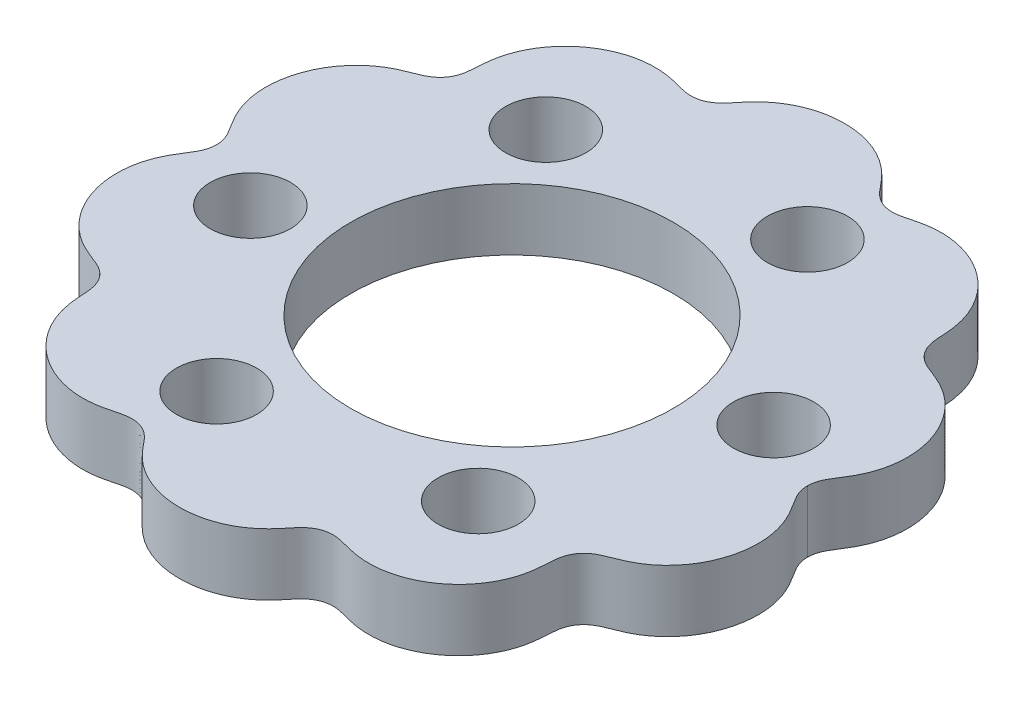
SolidWorks part; units mm, degrees
ref_plane "Front Plane" through (0, 0, 0) normal (0, 0, 1) x (1, 0, 0)
ref_plane "Top Plane" through (0, 0, 0) normal (0, 1, 0) x (1, 0, 0)
ref_plane "Right Plane" through (0, 0, 0) normal (1, 0, 0) x (0, 0, -1)
sketch "Sketch1" plane through (0, 0, 0) normal (0, 1, 0) x (1, 0, 0)
  spline S0 degree 4 poles (25.7906, 7.5343) (25.8788, 7.1133) (25.9899, 6.258) (25.9622, 5.173) (25.6669, 3.909) (25.2966, 3.0278) (25.0022, 2.4855) (24.7411, 2.0653) (24.5631, 1.7918) (24.4128, 1.5559) (24.2753, 1.3229) (24.1728, 1.1289) (24.0852, 0.9325) (24.0168, 0.7401) (23.9736, 0.5903) (23.9409, 0.4443) (23.918, 0.3017) (23.9061, 0.188) (23.9012, 0.082) (23.8998, 0.0096) (23.9001, -0.0378) (23.9031, -0.1354) (23.9124, -0.2583) (23.931, -0.3897) (23.9595, -0.5322) (23.992, -0.6548) (24.033, -0.7865) (24.0838, -0.9249) (24.1521, -1.083) (24.2429, -1.2629) (24.3447, -1.4425) (24.4552, -1.6225) (24.5717, -1.8045) (24.7183, -2.0313) (24.8914, -2.3053) (25.0875, -2.6402) (25.2934, -3.0428) (25.5234, -3.5754) (25.7435, -4.2491) (25.909, -5.0602) (25.989, -6.24) (25.8643, -7.4222) (25.5418, -8.5683) (25.0323, -9.6423) (24.5159, -10.4451) (23.8988, -11.1736) (23.1893, -11.8124) (22.5069, -12.2735) (21.8941, -12.5927) (21.3804, -12.8129) (20.9812, -12.967) (20.5083, -13.1497) (20.0028, -13.3924) (19.5163, -13.7704) (19.1071, -14.3429) (18.9044, -14.9387) (18.8377, -15.5108) (18.8117, -16.0408) (18.7845, -16.4899) (18.7247, -17.0578) (18.5966, -17.7393) (18.287, -18.7429) (17.6345, -19.995) (16.5677, -21.2689) (15.0187, -22.3804) (13.232, -23.0712) (11.6863, -23.2335) (10.5209, -23.1072) (9.745, -22.9271) (9.3314, -22.8175) (8.8415, -22.6876) (8.2891, -22.5904) (7.675, -22.6156) (7.014, -22.8425) (6.5078, -23.2036) (6.1238, -23.6204) (5.7973, -24.0261) (5.517, -24.3664) (4.9887, -24.958) (4.1217, -25.7163) (2.8002, -26.4589) (0.9866, -26.9323) (-0.8925, -26.9446) (-2.4927, -26.549) (-3.7586, -25.9235) (-4.6012, -25.2962) (-5.1069, -24.8217) (-5.4903, -24.3984) (-5.7768, -24.0514) (-6.1092, -23.6377) (-6.4971, -23.212) (-7.008, -22.8447) (-7.6734, -22.6157) (-8.2891, -22.5904) (-8.8414, -22.6876) (-9.3314, -22.8175) (-9.745, -22.9271) (-10.5209, -23.1072) (-11.6863, -23.2335) (-13.232, -23.0712) (-15.0187, -22.3804) (-16.5677, -21.2689) (-17.6345, -19.995) (-18.287, -18.7429) (-18.5966, -17.7393) (-18.7247, -17.0578) (-18.7845, -16.4899) (-18.8117, -16.0408) (-18.8377, -15.5108) (-18.9044, -14.9387) (-19.1071, -14.3429) (-19.5163, -13.7704) (-20.0028, -13.3924) (-20.5083, -13.1497) (-20.9812, -12.967) (-21.3804, -12.8129) (-21.8941, -12.5927) (-22.5069, -12.2735) (-23.1893, -11.8124) (-23.8988, -11.1736) (-24.5159, -10.4451) (-25.0323, -9.6423) (-25.5418, -8.5683) (-25.8643, -7.4222) (-25.989, -6.24) (-25.909, -5.0602) (-25.7435, -4.2491) (-25.5234, -3.5754) (-25.2934, -3.0428) (-25.0875, -2.6402) (-24.8914, -2.3053) (-24.7183, -2.0313) (-24.5717, -1.8045) (-24.4552, -1.6225) (-24.3447, -1.4425) (-24.2429, -1.2629) (-24.1521, -1.083) (-24.0838, -0.9249) (-24.033, -0.7865) (-23.992, -0.6548) (-23.9595, -0.5322) (-23.931, -0.3897) (-23.9124, -0.2583) (-23.9031, -0.1354) (-23.9001, -0.0378) (-23.8998, 0.0096) (-23.9012, 0.082) (-23.9061, 0.188) (-23.918, 0.3017) (-23.9409, 0.4443) (-23.9736, 0.5903) (-24.0168, 0.7401) (-24.0852, 0.9325) (-24.1918, 1.1715) (-24.3429, 1.4455) (-24.5376, 1.7528) (-24.7411, 2.0653) (-25.0022, 2.4855) (-25.2966, 3.0278) (-25.6669, 3.909) (-25.9622, 5.173) (-25.9899, 6.258) (-25.8788, 7.1133) (-25.7906, 7.5343) knots 0 0 0 0 0 0.016557 0.033114 0.041392 0.04967 0.053259 0.056848 0.060437 0.062231 0.064026 0.067263 0.068881 0.0705 0.071881 0.073262 0.074643 0.076024 0.076447 0.07687 0.077627 0.078384 0.079897 0.081411 0.082924 0.083871 0.084817 0.08671 0.088602 0.090495 0.092574 0.094654 0.096734 0.098813 0.102972 0.107132 0.111671 0.11621 0.125289 0.134368 0.143447 0.161605 0.170766 0.179928 0.18909 0.198252 0.207413 0.216574 0.220692 0.22481 0.228927 0.233045 0.240218 0.246328 0.252328 0.259785 0.264113 0.268441 0.27277 0.277098 0.286094 0.29509 0.313082 0.331073 0.349394 0.367716 0.386036 0.390153 0.39427 0.398387 0.402504 0.409677 0.415786 0.421726 0.429063 0.433304 0.437545 0.441787 0.446028 0.463838 0.481648 0.499458 0.517452 0.535446 0.544443 0.55344 0.557769 0.562098 0.566426 0.570755 0.578213 0.584214 0.590323 0.597496 0.601613 0.60573 0.609847 0.613964 0.632284 0.650606 0.668927 0.686918 0.70491 0.713906 0.722902 0.72723 0.731559 0.735887 0.740215 0.747672 0.753672 0.759782 0.766955 0.771073 0.77519 0.779308 0.783426 0.792587 0.801748 0.81091 0.820072 0.829234 0.838395 0.856553 0.865632 0.874711 0.88379 0.888329 0.892868 0.897028 0.901187 0.903266 0.905346 0.907426 0.909505 0.911398 0.91329 0.915183 0.916129 0.917076 0.918589 0.920103 0.921616 0.922373 0.92313 0.923553 0.923976 0.925357 0.926738 0.928119 0.9295 0.931119 0.932737 0.935974 0.939563 0.943152 0.946741 0.95033 0.958608 0.966886 0.983443 1 1 1 1 1 construction
  spline S1 degree 4 poles (23.9, 0) (23.9, -0.0166) (23.9004, -0.0497) (23.9031, -0.1354) (23.9124, -0.2583) (23.931, -0.3897) (23.9595, -0.5322) (23.992, -0.6548) (24.033, -0.7865) (24.0838, -0.9249) (24.1521, -1.083) (24.2429, -1.2629) (24.3447, -1.4425) (24.4552, -1.6225) (24.5717, -1.8045) (24.7183, -2.0313) (24.8914, -2.3053) (25.0875, -2.6402) (25.2934, -3.0428) (25.5234, -3.5754) (25.7435, -4.2491) (25.909, -5.0602) (25.989, -6.24) (25.8643, -7.4222) (25.5418, -8.5683) (25.0323, -9.6423) (24.5159, -10.4451) (23.8988, -11.1736) (23.1893, -11.8124) (22.5069, -12.2735) (21.8941, -12.5927) (21.3804, -12.8129) (20.9812, -12.967) (20.5083, -13.1497) (20.0028, -13.3924) (19.5163, -13.7704) (19.1071, -14.3429) (18.9044, -14.9387) (18.8377, -15.5108) (18.8117, -16.0408) (18.7845, -16.4899) (18.7247, -17.0578) (18.5966, -17.7393) (18.287, -18.7429) (17.6345, -19.995) (16.5677, -21.2689) (15.0187, -22.3804) (13.232, -23.0712) (11.6863, -23.2335) (10.5209, -23.1072) (9.745, -22.9271) (9.3314, -22.8175) (8.8415, -22.6876) (8.2891, -22.5904) (7.675, -22.6156) (7.014, -22.8425) (6.5078, -23.2036) (6.1238, -23.6204) (5.7973, -24.0261) (5.517, -24.3664) (4.9887, -24.958) (4.1217, -25.7163) (2.8002, -26.4589) (0.9866, -26.9323) (-0.8925, -26.9446) (-2.4927, -26.549) (-3.7586, -25.9235) (-4.6012, -25.2962) (-5.1069, -24.8217) (-5.4903, -24.3984) (-5.7768, -24.0514) (-6.1092, -23.6377) (-6.4971, -23.212) (-7.008, -22.8447) (-7.6734, -22.6157) (-8.2891, -22.5904) (-8.8414, -22.6876) (-9.3314, -22.8175) (-9.745, -22.9271) (-10.5209, -23.1072) (-11.6863, -23.2335) (-13.232, -23.0712) (-15.0187, -22.3804) (-16.5677, -21.2689) (-17.6345, -19.995) (-18.287, -18.7429) (-18.5966, -17.7393) (-18.7247, -17.0578) (-18.7845, -16.4899) (-18.8117, -16.0408) (-18.8377, -15.5108) (-18.9044, -14.9387) (-19.1071, -14.3429) (-19.5163, -13.7704) (-20.0028, -13.3924) (-20.5083, -13.1497) (-20.9812, -12.967) (-21.3804, -12.8129) (-21.8941, -12.5927) (-22.5069, -12.2735) (-23.1893, -11.8124) (-23.8988, -11.1736) (-24.5159, -10.4451) (-25.0323, -9.6423) (-25.5418, -8.5683) (-25.8643, -7.4222) (-25.989, -6.24) (-25.909, -5.0602) (-25.7435, -4.2491) (-25.5234, -3.5754) (-25.2934, -3.0428) (-25.0875, -2.6402) (-24.8914, -2.3053) (-24.7183, -2.0313) (-24.5717, -1.8045) (-24.4552, -1.6225) (-24.3447, -1.4425) (-24.2429, -1.2629) (-24.1521, -1.083) (-24.0838, -0.9249) (-24.033, -0.7865) (-23.992, -0.6548) (-23.9595, -0.5322) (-23.931, -0.3897) (-23.9124, -0.2583) (-23.9031, -0.1354) (-23.9004, -0.0497) (-23.9, -0.0166) (-23.9, 0) knots 0.07687 0.07687 0.07687 0.07687 0.07687 0.077627 0.078384 0.079897 0.081411 0.082924 0.083871 0.084817 0.08671 0.088602 0.090495 0.092574 0.094654 0.096734 0.098813 0.102972 0.107132 0.111671 0.11621 0.125289 0.134368 0.143447 0.161605 0.170766 0.179928 0.18909 0.198252 0.207413 0.216574 0.220692 0.22481 0.228927 0.233045 0.240218 0.246328 0.252328 0.259785 0.264113 0.268441 0.27277 0.277098 0.286094 0.29509 0.313082 0.331073 0.349394 0.367716 0.386036 0.390153 0.39427 0.398387 0.402504 0.409677 0.415786 0.421726 0.429063 0.433304 0.437545 0.441787 0.446028 0.463838 0.481648 0.499458 0.517452 0.535446 0.544443 0.55344 0.557769 0.562098 0.566426 0.570755 0.578213 0.584214 0.590323 0.597496 0.601613 0.60573 0.609847 0.613964 0.632284 0.650606 0.668927 0.686918 0.70491 0.713906 0.722902 0.72723 0.731559 0.735887 0.740215 0.747672 0.753672 0.759782 0.766955 0.771073 0.77519 0.779308 0.783426 0.792587 0.801748 0.81091 0.820072 0.829234 0.838395 0.856553 0.865632 0.874711 0.88379 0.888329 0.892868 0.897028 0.901187 0.903266 0.905346 0.907426 0.909505 0.911398 0.91329 0.915183 0.916129 0.917076 0.918589 0.920103 0.921616 0.922373 0.92313 0.92313 0.92313 0.92313 0.92313
  spline S2 degree 4 poles (-25.7906, -7.5343) (-25.8788, -7.1133) (-25.9899, -6.258) (-25.9622, -5.173) (-25.6669, -3.909) (-25.2966, -3.0278) (-25.0022, -2.4855) (-24.7411, -2.0653) (-24.5631, -1.7918) (-24.4128, -1.5559) (-24.2753, -1.3229) (-24.1728, -1.1289) (-24.0852, -0.9325) (-24.0168, -0.7401) (-23.9736, -0.5903) (-23.9409, -0.4443) (-23.918, -0.3017) (-23.9061, -0.188) (-23.9012, -0.082) (-23.8998, -0.0096) (-23.9001, 0.0378) (-23.9031, 0.1354) (-23.9124, 0.2583) (-23.931, 0.3897) (-23.9595, 0.5322) (-23.992, 0.6548) (-24.033, 0.7865) (-24.0838, 0.9249) (-24.1521, 1.083) (-24.2429, 1.2629) (-24.3447, 1.4425) (-24.4552, 1.6225) (-24.5717, 1.8045) (-24.7183, 2.0313) (-24.8914, 2.3053) (-25.0875, 2.6402) (-25.2934, 3.0428) (-25.5234, 3.5754) (-25.7435, 4.2491) (-25.909, 5.0602) (-25.989, 6.24) (-25.8643, 7.4222) (-25.5418, 8.5683) (-25.0323, 9.6423) (-24.5159, 10.4451) (-23.8988, 11.1736) (-23.1893, 11.8124) (-22.5069, 12.2735) (-21.8941, 12.5927) (-21.3804, 12.8129) (-20.9812, 12.967) (-20.5083, 13.1497) (-20.0028, 13.3924) (-19.5163, 13.7704) (-19.1071, 14.3429) (-18.9044, 14.9387) (-18.8377, 15.5108) (-18.8117, 16.0408) (-18.7845, 16.4899) (-18.7247, 17.0578) (-18.5966, 17.7393) (-18.287, 18.7429) (-17.6345, 19.995) (-16.5677, 21.2689) (-15.0187, 22.3804) (-13.232, 23.0712) (-11.6863, 23.2335) (-10.5209, 23.1072) (-9.745, 22.9271) (-9.3314, 22.8175) (-8.8415, 22.6876) (-8.2891, 22.5904) (-7.675, 22.6156) (-7.014, 22.8425) (-6.5078, 23.2036) (-6.1238, 23.6204) (-5.7973, 24.0261) (-5.517, 24.3664) (-4.9887, 24.958) (-4.1217, 25.7163) (-2.8002, 26.4589) (-0.9866, 26.9323) (0.8925, 26.9446) (2.4927, 26.549) (3.7586, 25.9235) (4.6012, 25.2962) (5.1069, 24.8217) (5.4903, 24.3984) (5.7768, 24.0514) (6.1092, 23.6377) (6.4971, 23.212) (7.008, 22.8447) (7.6734, 22.6157) (8.2891, 22.5904) (8.8414, 22.6876) (9.3314, 22.8175) (9.745, 22.9271) (10.5209, 23.1072) (11.6863, 23.2335) (13.232, 23.0712) (15.0187, 22.3804) (16.5677, 21.2689) (17.6345, 19.995) (18.287, 18.7429) (18.5966, 17.7393) (18.7247, 17.0578) (18.7845, 16.4899) (18.8117, 16.0408) (18.8377, 15.5108) (18.9044, 14.9387) (19.1071, 14.3429) (19.5163, 13.7704) (20.0028, 13.3924) (20.5083, 13.1497) (20.9812, 12.967) (21.3804, 12.8129) (21.8941, 12.5927) (22.5069, 12.2735) (23.1893, 11.8124) (23.8988, 11.1736) (24.5159, 10.4451) (25.0323, 9.6423) (25.5418, 8.5683) (25.8643, 7.4222) (25.989, 6.24) (25.909, 5.0602) (25.7435, 4.2491) (25.5234, 3.5754) (25.2934, 3.0428) (25.0875, 2.6402) (24.8914, 2.3053) (24.7183, 2.0313) (24.5717, 1.8045) (24.4552, 1.6225) (24.3447, 1.4425) (24.2429, 1.2629) (24.1521, 1.083) (24.0838, 0.9249) (24.033, 0.7865) (23.992, 0.6547) (23.9595, 0.5322) (23.931, 0.3896) (23.9124, 0.2584) (23.9031, 0.135) (23.8997, 0.0263) (23.8998, -0.0438) (23.905, -0.1791) (23.918, -0.3009) (23.9409, -0.4447) (23.9736, -0.5901) (24.0168, -0.7402) (24.0852, -0.9325) (24.1918, -1.1716) (24.3429, -1.4455) (24.5376, -1.7528) (24.7411, -2.0653) (25.0022, -2.4855) (25.2966, -3.0278) (25.6669, -3.9091) (25.9622, -5.173) (25.9899, -6.258) (25.8788, -7.1133) (25.7906, -7.5343) knots 0 0 0 0 0 0.016557 0.033114 0.041392 0.04967 0.053259 0.056848 0.060437 0.062231 0.064026 0.067263 0.068881 0.0705 0.071881 0.073262 0.074643 0.076024 0.076447 0.07687 0.077627 0.078384 0.079897 0.081411 0.082924 0.083871 0.084817 0.08671 0.088602 0.090495 0.092574 0.094654 0.096734 0.098813 0.102972 0.107132 0.111671 0.11621 0.125289 0.134368 0.143447 0.161605 0.170766 0.179928 0.18909 0.198252 0.207413 0.216574 0.220692 0.22481 0.228927 0.233045 0.240218 0.246328 0.252328 0.259785 0.264113 0.268441 0.27277 0.277098 0.286094 0.29509 0.313082 0.331073 0.349394 0.367716 0.386036 0.390153 0.39427 0.398387 0.402504 0.409677 0.415786 0.421726 0.429063 0.433304 0.437545 0.441787 0.446028 0.463838 0.481648 0.499458 0.517452 0.535446 0.544443 0.55344 0.557769 0.562098 0.566426 0.570755 0.578213 0.584214 0.590323 0.597496 0.601613 0.60573 0.609847 0.613964 0.632284 0.650606 0.668927 0.686918 0.70491 0.713906 0.722902 0.72723 0.731559 0.735887 0.740215 0.747672 0.753672 0.759782 0.766955 0.771073 0.77519 0.779308 0.783426 0.792587 0.801748 0.81091 0.820072 0.829234 0.838395 0.856553 0.865632 0.874711 0.88379 0.888329 0.892868 0.897028 0.901187 0.903266 0.905346 0.907426 0.909505 0.911398 0.91329 0.915183 0.916129 0.917076 0.918589 0.920103 0.921616 0.922373 0.92313 0.923976 0.925357 0.926738 0.928119 0.9295 0.931119 0.932737 0.935974 0.939563 0.943152 0.946741 0.95033 0.958608 0.966886 0.983443 1 1 1 1 1 construction
  spline S3 degree 4 poles (-23.9, 0) (-23.9, 0.0166) (-23.9004, 0.0497) (-23.9031, 0.1354) (-23.9124, 0.2583) (-23.931, 0.3897) (-23.9595, 0.5322) (-23.992, 0.6548) (-24.033, 0.7865) (-24.0838, 0.9249) (-24.1521, 1.083) (-24.2429, 1.2629) (-24.3447, 1.4425) (-24.4552, 1.6225) (-24.5717, 1.8045) (-24.7183, 2.0313) (-24.8914, 2.3053) (-25.0875, 2.6402) (-25.2934, 3.0428) (-25.5234, 3.5754) (-25.7435, 4.2491) (-25.909, 5.0602) (-25.989, 6.24) (-25.8643, 7.4222) (-25.5418, 8.5683) (-25.0323, 9.6423) (-24.5159, 10.4451) (-23.8988, 11.1736) (-23.1893, 11.8124) (-22.5069, 12.2735) (-21.8941, 12.5927) (-21.3804, 12.8129) (-20.9812, 12.967) (-20.5083, 13.1497) (-20.0028, 13.3924) (-19.5163, 13.7704) (-19.1071, 14.3429) (-18.9044, 14.9387) (-18.8377, 15.5108) (-18.8117, 16.0408) (-18.7845, 16.4899) (-18.7247, 17.0578) (-18.5966, 17.7393) (-18.287, 18.7429) (-17.6345, 19.995) (-16.5677, 21.2689) (-15.0187, 22.3804) (-13.232, 23.0712) (-11.6863, 23.2335) (-10.5209, 23.1072) (-9.745, 22.9271) (-9.3314, 22.8175) (-8.8415, 22.6876) (-8.2891, 22.5904) (-7.675, 22.6156) (-7.014, 22.8425) (-6.5078, 23.2036) (-6.1238, 23.6204) (-5.7973, 24.0261) (-5.517, 24.3664) (-4.9887, 24.958) (-4.1217, 25.7163) (-2.8002, 26.4589) (-0.9866, 26.9323) (0.8925, 26.9446) (2.4927, 26.549) (3.7586, 25.9235) (4.6012, 25.2962) (5.1069, 24.8217) (5.4903, 24.3984) (5.7768, 24.0514) (6.1092, 23.6377) (6.4971, 23.212) (7.008, 22.8447) (7.6734, 22.6157) (8.2891, 22.5904) (8.8414, 22.6876) (9.3314, 22.8175) (9.745, 22.9271) (10.5209, 23.1072) (11.6863, 23.2335) (13.232, 23.0712) (15.0187, 22.3804) (16.5677, 21.2689) (17.6345, 19.995) (18.287, 18.7429) (18.5966, 17.7393) (18.7247, 17.0578) (18.7845, 16.4899) (18.8117, 16.0408) (18.8377, 15.5108) (18.9044, 14.9387) (19.1071, 14.3429) (19.5163, 13.7704) (20.0028, 13.3924) (20.5083, 13.1497) (20.9812, 12.967) (21.3804, 12.8129) (21.8941, 12.5927) (22.5069, 12.2735) (23.1893, 11.8124) (23.8988, 11.1736) (24.5159, 10.4451) (25.0323, 9.6423) (25.5418, 8.5683) (25.8643, 7.4222) (25.989, 6.24) (25.909, 5.0602) (25.7435, 4.2491) (25.5234, 3.5754) (25.2934, 3.0428) (25.0875, 2.6402) (24.8914, 2.3053) (24.7183, 2.0313) (24.5717, 1.8045) (24.4552, 1.6225) (24.3447, 1.4425) (24.2429, 1.2629) (24.1521, 1.083) (24.0838, 0.9249) (24.033, 0.7865) (23.992, 0.6547) (23.9595, 0.5322) (23.931, 0.3896) (23.9124, 0.2584) (23.9031, 0.135) (23.9004, 0.0501) (23.9, 0.0166) (23.9, 0) knots 0.07687 0.07687 0.07687 0.07687 0.07687 0.077627 0.078384 0.079897 0.081411 0.082924 0.083871 0.084817 0.08671 0.088602 0.090495 0.092574 0.094654 0.096734 0.098813 0.102972 0.107132 0.111671 0.11621 0.125289 0.134368 0.143447 0.161605 0.170766 0.179928 0.18909 0.198252 0.207413 0.216574 0.220692 0.22481 0.228927 0.233045 0.240218 0.246328 0.252328 0.259785 0.264113 0.268441 0.27277 0.277098 0.286094 0.29509 0.313082 0.331073 0.349394 0.367716 0.386036 0.390153 0.39427 0.398387 0.402504 0.409677 0.415786 0.421726 0.429063 0.433304 0.437545 0.441787 0.446028 0.463838 0.481648 0.499458 0.517452 0.535446 0.544443 0.55344 0.557769 0.562098 0.566426 0.570755 0.578213 0.584214 0.590323 0.597496 0.601613 0.60573 0.609847 0.613964 0.632284 0.650606 0.668927 0.686918 0.70491 0.713906 0.722902 0.72723 0.731559 0.735887 0.740215 0.747672 0.753672 0.759782 0.766955 0.771073 0.77519 0.779308 0.783426 0.792587 0.801748 0.81091 0.820072 0.829234 0.838395 0.856553 0.865632 0.874711 0.88379 0.888329 0.892868 0.897028 0.901187 0.903266 0.905346 0.907426 0.909505 0.911398 0.91329 0.915183 0.916129 0.917076 0.918589 0.920103 0.921616 0.922373 0.92313 0.92313 0.92313 0.92313 0.92313
extrude "Boss-Extrude1" add sketch "Sketch1" along normal blind 5
sketch "Sketch2" plane through (0, 5, 0) normal (0, 1, 0) x (1, 0, 0)
  circle A0 centre (0, 0) radius 13.05
  dimension "D1" = 26.1
extrude "Cut-Extrude1" cut sketch "Sketch2" against normal through all
sketch "Sketch3" plane through (0, 5, 0) normal (0, 1, 0) x (1, 0, 0)
  line L0 (0, 0) -> (33.4644, 0) construction
  line L1 (-2.75, 0) -> (2.75, 0) construction
  line L2 (0, 0) -> (18.2722, 2.894) construction
  circle A0 centre (18.2722, 2.894) radius 3.25
  dimension "D3" = 6.5
  dimension "D1" = 9
  dimension "D2" = 18.5
extrude "Cut-Extrude2" cut sketch "Sketch3" against normal through all
pattern_circular "CirPattern1" count 6 over 360 about axis through (0, 5, 0) along (0, 1, 0) of "Cut-Extrude2"
equation "\"pin_circle_R\" = 27"
equation "\"ecc\" = 1.5"
equation "\"n_pins\" = 11"
equation "\"pin_d\" = 3"
equation "\"out_pin_R\" = 18.5"
equation "\"disc_clr\" = 0.1"
equation "\"seat_6803\" = 26.1"
equation "\"disc_t\" = 5"
equation "\"D1@Sketch2\"=\"seat_6803\""
equation "\"D2@Sketch3\"=\"out_pin_R\""
equation "\"D3@Sketch3\"=\"pin_d\" + 2*\"ecc\" + \"out_hole_clr\""
equation "\"out_hole_clr\" = 0.5"
equation "\"seat_6806\" = 42.1"
equation "\"boss_17\" = 17.15"
equation "\"rotor_bolt_R\" = 10"
equation "\"m25_clr\" = 2.8"
equation "\"m25_head\" = 5"
equation "\"insert_hole\" = 4.4"
equation "\"csk\" = 0.6"
equation "\"peg_d\" = 3.0"
equation "\"plug_d\" = 8.6"
equation "\"peg_clr\" = 0.3"
equation "\"m3_clr\" = 3.4"
equation "\"m3_head\" = 6.2"
equation "\"pin_press\" = 3.2"
equation "\"pin_slip\" = 3.3"
equation "\"hub_30\" = 30.25"
equation "\"hub_short\" = 0.2"
equation "\"m3_tap\" = 2.8"
equation "\"rear_plate_t\" = 2"
